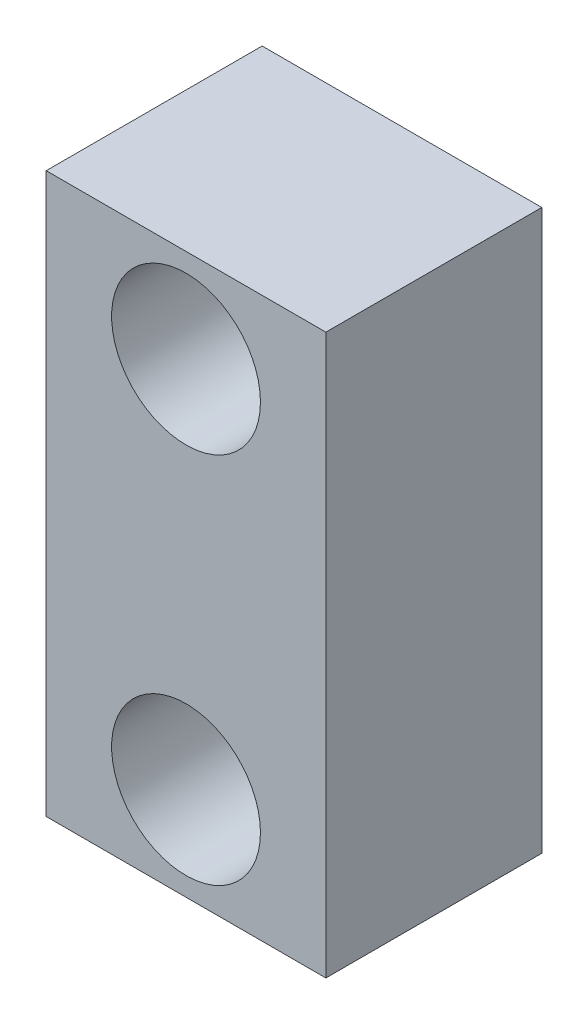
SolidWorks part; units mm, degrees
ref_plane "Front Plane" through (0, 0, 0) normal (0, 0, 1) x (1, 0, 0)
ref_plane "Top Plane" through (0, 0, 0) normal (0, 1, 0) x (1, 0, 0)
ref_plane "Right Plane" through (0, 0, 0) normal (1, 0, 0) x (0, 0, -1)
sketch "Sketch1" plane through (0, 0, 0) normal (0, 0, 1) x (1, 0, 0)
  line L0 (-15, -10) -> (0, 0) construction
  line L1 (-15, 50.0003) -> (15, 50.0003)
  line L2 (-15, 50.0003) -> (-15, -10)
  line L3 (-15, -10) -> (15, -10)
  line L4 (15, 50.0003) -> (15, -10)
  line L5 (0, 0) -> (15, -10) construction
  line L6 (-15, 50.0003) -> (0, 40.0003) construction
  line L7 (0, 40.0003) -> (15, 50.0003) construction
  circle A0 centre (0, 0) radius 7.9823
  circle A1 centre (0, 40.0003) radius 7.9823
  dimension "D3" = 30
  dimension "D4" = 15.9646
  dimension "D1" = 40.0003
  dimension "D2" = 10
extrude "Boss-Extrude1" add sketch "Sketch1" along normal blind 23.1638
